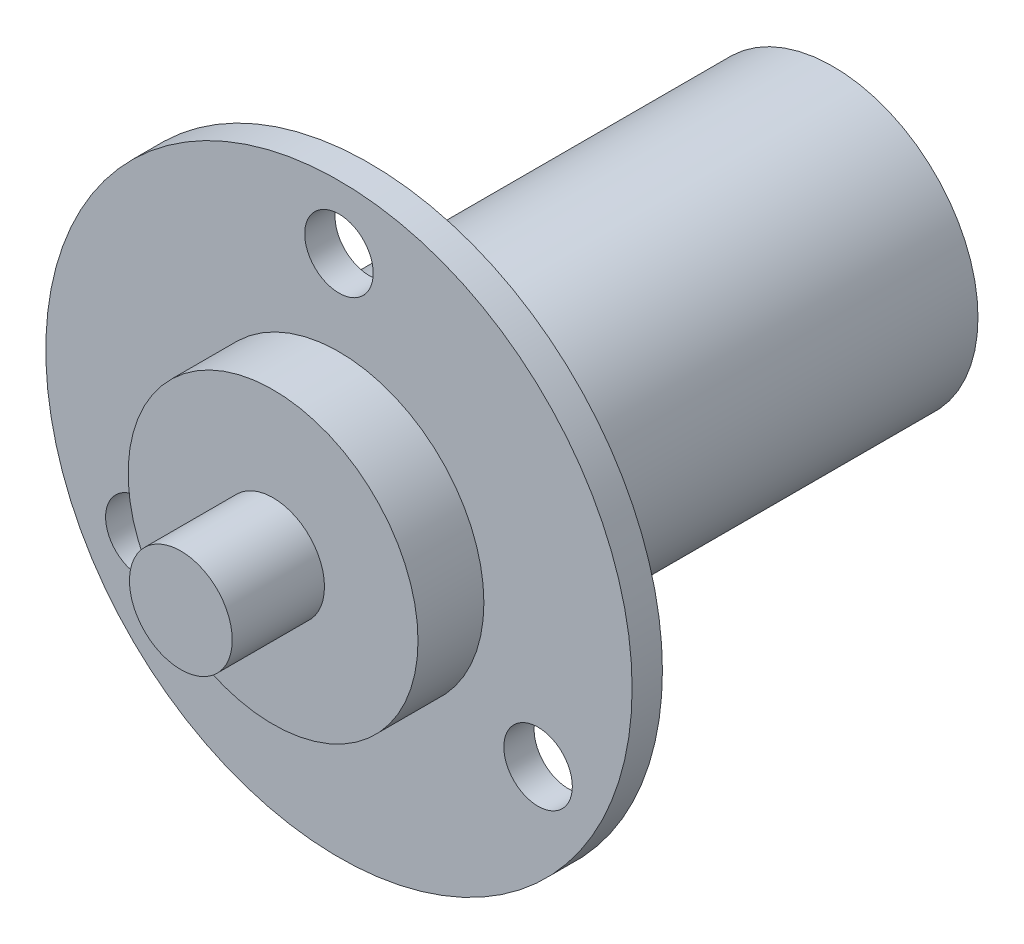
SolidWorks part; units mm, degrees
ref_plane "Front Plane" through (0, 0, 0) normal (0, 0, 1) x (1, 0, 0)
ref_plane "Top Plane" through (0, 0, 0) normal (0, 1, 0) x (1, 0, 0)
ref_plane "Right Plane" through (0, 0, 0) normal (1, 0, 0) x (0, 0, -1)
sketch "Sketch1" plane through (0, 0, 0) normal (0, 0, 1) x (1, 0, 0)
  line L0 (0, 0) -> (-15.1121, -8.725) construction
  circle A0 centre (0, 0) radius 11
  circle A1 centre (0, 0) radius 22.25
  circle A2 centre (0, 0) radius 17.45 construction
  circle A3 centre (0, 17.45) radius 2.6
  circle A4 centre (15.1121, -8.725) radius 2.6
  circle A5 centre (-15.1121, -8.725) radius 2.6
  circle A6 centre (0, 0) radius 3.9
  point P14 (0, 0)
  dimension "D1" = 22
  dimension "D2" = 44.5
  dimension "D3" = 34.9
  dimension "D4" = 5.2
  dimension "D7" = 7.8
  dimension "D6" = 120
  dimension "D5" = 3
extrude "Boss-Extrude1" add sketch "Sketch1" along normal blind 5 and the other way blind 37.5 contours A0 A6 region at (-10.6889, 0, 0)
extrude "Boss-Extrude2" add sketch "Sketch1<3>" against normal blind 2.3 contours A1 A5 A4 A3 A0 region at (-21.6207, 0, 0)
sketch "Sketch1<3>" plane through (0, 0, 0) normal (0, 0, 1) x (1, 0, 0) same geometry as "Sketch1"
extrude "Boss-Extrude4" add sketch "Sketch1<4>" along normal blind 12 and the other way up to surface (37.5 mm away) contours A6 region at (0, 0, 0) other way up to face at (3.9, 0, -37.5)
sketch "Sketch1<4>" plane through (0, 0, 0) normal (0, 0, 1) x (1, 0, 0) same geometry as "Sketch1"
